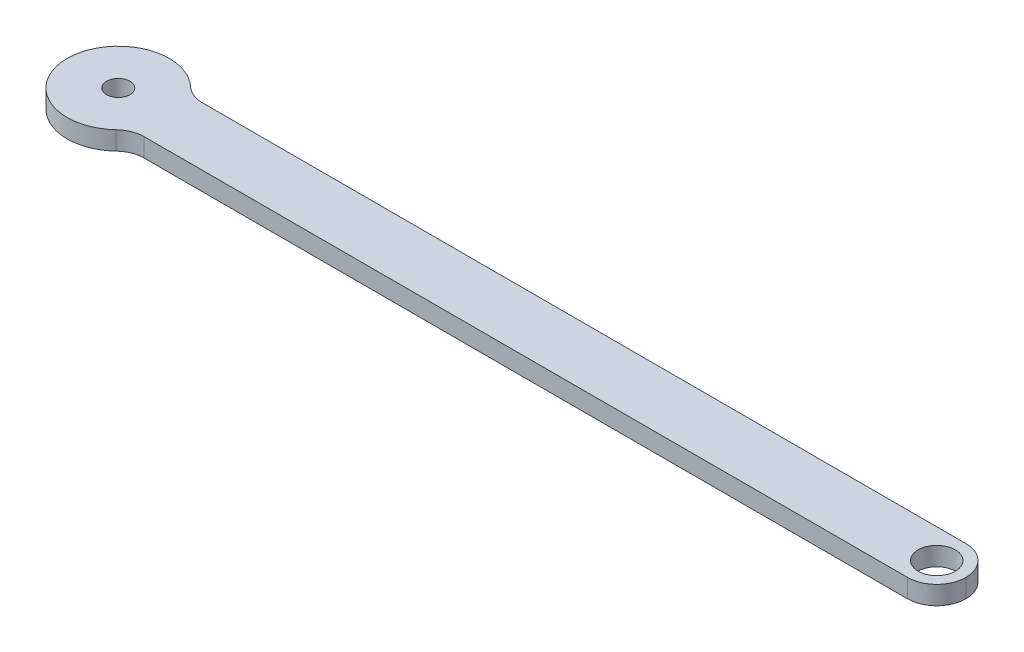
SolidWorks part; units mm, degrees
material "ABS"
ref_plane "Front Plane" through (0, 0, 0) normal (0, 0, 1) x (1, 0, 0)
ref_plane "Top Plane" through (0, 0, 0) normal (0, 1, 0) x (1, 0, 0)
ref_plane "Right Plane" through (0, 0, 0) normal (1, 0, 0) x (0, 0, -1)
sketch "Sketch1" plane through (0, 0, 0) normal (0, 1, 0) x (1, 0, 0)
  line L1 (-150, 10) -> (150, 10)
  line L2 (-150, 10) -> (-150, -10)
  line L3 (-150, -10) -> (150, -10)
  line L4 (150, 10) -> (150, -10)
  point P4 (0, -10)
  point P5 (0, 10)
  point P9 (150, 0)
  dimension "D1" = 300
  dimension "D2" = 20
extrude "Boss-Extrude1" add sketch "Sketch1" along normal blind 6.35
sketch "Sketch2" plane through (0, 0, 0) normal (0, -1, 0) x (-1, 0, 0)
  line L0 (-3.4925, 0) -> (3.4925, 0) construction
  line L1 (150, 10) -> (150, -10) construction
  circle A0 centre (140, 0) radius 6.35
  dimension "D1" = 12.7
  dimension "D2" = 10
extrude "Cut-Extrude1" cut sketch "Sketch2" against normal up to surface (6.35 mm away) up to face at (0, 6.35, 0)
mirror "Mirror1" about plane through (0, 0, 0) normal (1, 0, 0) of "Cut-Extrude1"
fillet "Congé1" radius 10 4 edges at (-150, 3.175, -10) (-150, 3.175, 10) (150, 3.175, -10) (150, 3.175, 10)
sketch "Sketch3" plane through (0, 6.35, 0) normal (0, 1, 0) x (1, 0, 0)
  circle A0 centre (-140, 0) radius 17.5
  circle A2 centre (-140, 0) radius 4
  circle A5 centre (-140, 0) radius 6.35 construction
  dimension "D1" = 35
  dimension "D2" = 8
extrude "Boss-Extrude2" add sketch "Sketch3" against normal up to surface (6.35 mm away) up to face at (140, 0, -6.35)
fillet "Fillet2" radius 10 2 edges at (-125.6386, 3.175, 10) (-125.6386, 3.175, -10)
